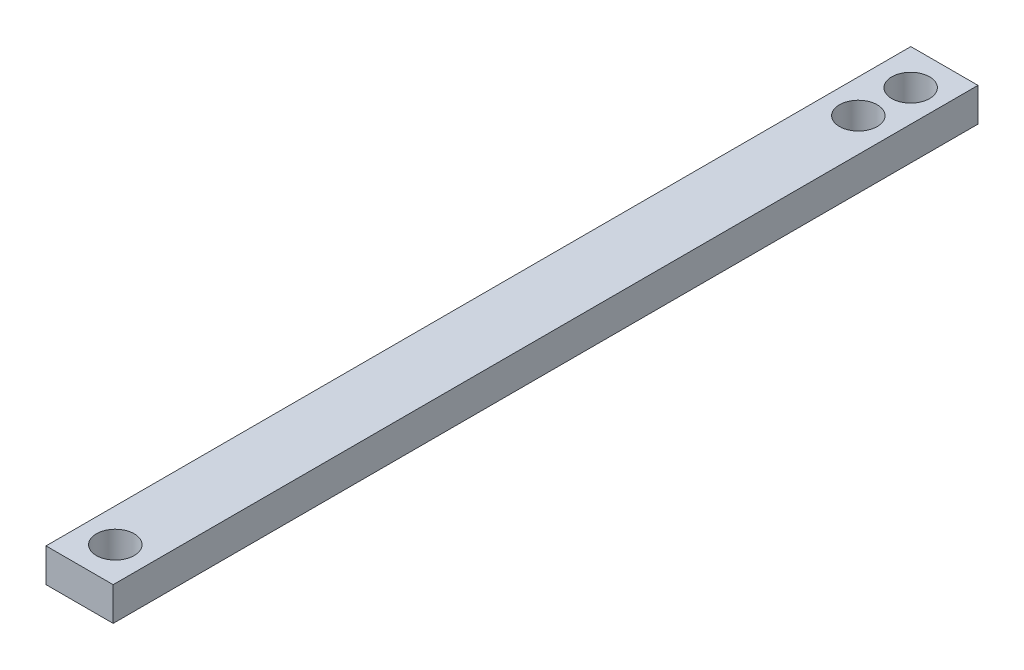
SolidWorks part; units mm, degrees
ref_plane "Front Plane" through (0, 0, 0) normal (0, 0, 1) x (1, 0, 0)
ref_plane "Top Plane" through (0, 0, 0) normal (0, 1, 0) x (1, 0, 0)
ref_plane "Right Plane" through (0, 0, 0) normal (1, 0, 0) x (0, 0, -1)
sketch "Sketch1" plane through (0, 0, 0) normal (0, 0, 1) x (1, 0, 0)
  line L1 (0, 0) -> (50.8, 0)
  line L2 (0, 0) -> (0, 25.4)
  line L3 (0, 25.4) -> (50.8, 25.4)
  line L4 (50.8, 0) -> (50.8, 25.4)
  dimension "D1" = 25.4
  dimension "D2" = 50.8
extrude "Boss-Extrude1" add sketch "Sketch1" along normal blind 615.95
sketch "Sketch2" plane through (0, 25.4, 0) normal (0, 1, 0) x (1, 0, 0)
  line L0 (50.8, -615.95) -> (0, -615.95) construction
  line L1 (50.8, -615.95) -> (50.8, 0) construction
  line L2 (50.8, 0) -> (0, 0) construction
  circle A0 centre (25.4, -588.9498) radius 14.3002
  circle A1 centre (25.4, -27.0002) radius 14.3002
  dimension "D1" = 28.6004
  dimension "D4" = 28.6004
  dimension "D2" = 27.0002
  dimension "D3" = 25.4
  dimension "D5" = 27.0002
  dimension "D6" = 25.4
extrude "Cut-Extrude1" cut sketch "Sketch2" against normal blind 762
sketch "Sketch3" plane through (0, 0, 0) normal (0, 0, -1) x (-1, 0, 0)
  line L1 (-50.8, 25.4) -> (0, 25.4)
  line L2 (-50.8, 25.4) -> (-50.8, 0)
  line L3 (-50.8, 0) -> (0, 0)
  line L4 (0, 25.4) -> (0, 0)
extrude "Boss-Extrude2" add sketch "Sketch3" along normal blind 38.1
sketch "Sketch4" plane through (0, 25.4, 0) normal (0, 1, 0) x (1, 0, 0)
  line L0 (0, 38.1) -> (50.8, 38.1) construction
  circle A0 centre (26.8822, 11.0998) radius 14.3002
  dimension "D1" = 28.6004
  dimension "D2" = 27.0002
extrude "Cut-Extrude2" cut sketch "Sketch4" against normal blind 101.6
